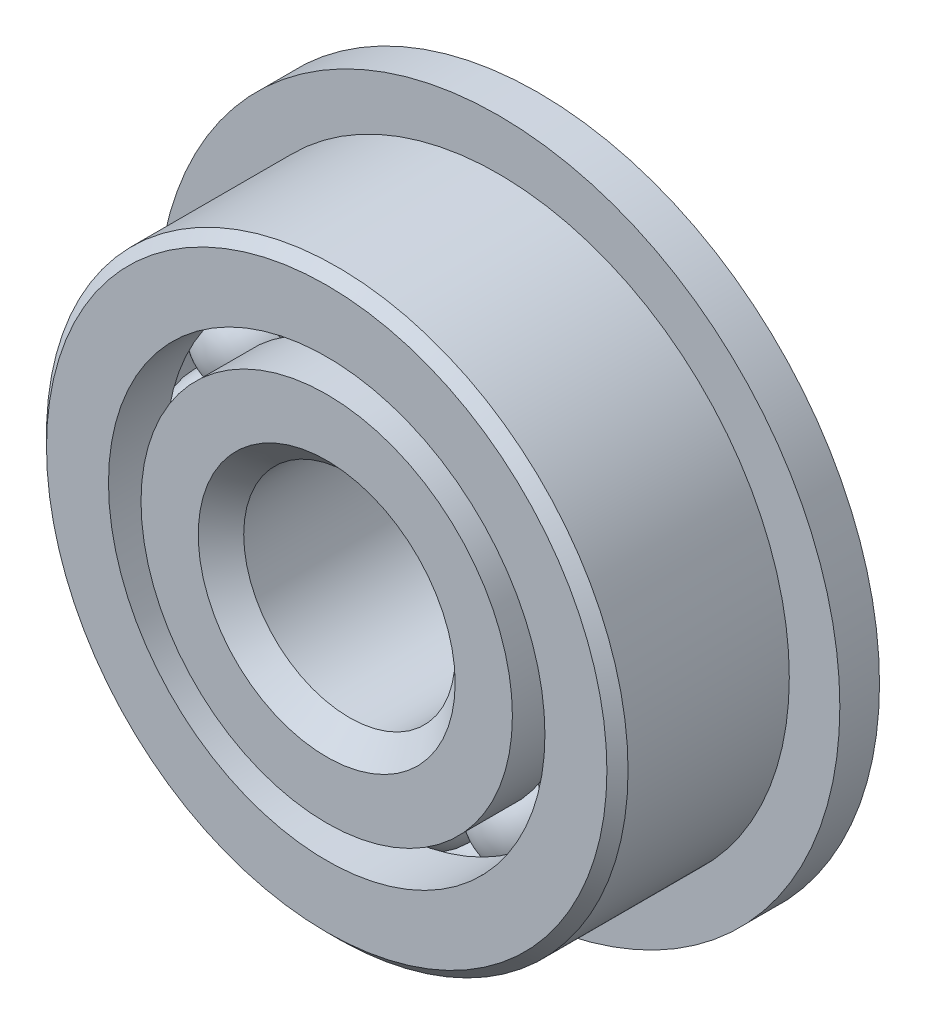
SolidWorks part; units mm, degrees
ref_plane "Front Plane" through (0, 0, 0) normal (0, 0, 1) x (1, 0, 0)
ref_plane "Top Plane" through (0, 0, 0) normal (0, 1, 0) x (1, 0, 0)
ref_plane "Right Plane" through (0, 0, 0) normal (1, 0, 0) x (0, 0, -1)
sketch "Sketch1" plane through (0, 0, 0) normal (1, 0, 0) x (0, 0, -1)
  line L0 (-3.175, 0) -> (3.175, 0) construction
  line L1 (0, 8.7312) -> (0, -8.7312) construction
  line L2 (2.8575, 8.7312) -> (-2.8575, 8.7312)
  line L3 (-2.8575, 8.7312) -> (-3.175, 8.4138)
  line L4 (-3.175, 8.4138) -> (-3.175, 6.5527)
  line L5 (-3.175, 6.5527) -> (-1.4436, 6.5527)
  line L6 (3.175, 6.5527) -> (1.4436, 6.5527)
  line L7 (3.175, 8.4138) -> (3.175, 6.5527)
  line L8 (2.8575, 8.7312) -> (3.175, 8.4138)
  line L9 (0, 8.7312) -> (0, 6.0643) construction
  line L11 (3.175, 0) -> (4.7625, 0) construction
  arc A0 (-1.4436, 6.5527) -> (1.4436, 6.5527) centre (0, 6.0643) cw
  circle A1 centre (0, 6.0643) radius 1.524 construction
  point P14 (0, 3.175)
  dimension "D3" = 3.048
  dimension "D1" = 45
  dimension "Width" = 6.35
  dimension "OD" = 17.4625
  dimension "D2" = 0.3175
  dimension "Shaft Dia" = 6.35
  dimension "D4" = 0.4885
  dimension "D5" = 2.667
  dimension "Total Wd" = 7.9375
revolve "Revolve1" add sketch "Sketch1" angle 360 about L0
sketch "Sketch2" plane through (0, 0, 0) normal (1, 0, 0) x (0, 0, -1)
  line L0 (-3.175, 5.5758) -> (-1.4436, 5.5758)
  line L1 (-3.175, 8.4138) -> (-3.175, -8.4138) construction
  line L2 (-3.175, 5.5758) -> (-3.175, 4.7167)
  line L3 (-3.175, 4.7167) -> (-2.3159, 3.8576)
  line L4 (-2.3159, 3.8576) -> (0, 3.8576)
  line L5 (0, 8.7312) -> (0, -8.7312) construction
  line L6 (0, 3.8576) -> (0, 4.5403)
  line L7 (0, 4.5403) -> (0, 3.175) construction
  line L8 (-3.175, 5.5758) -> (-3.175, 3.8576) construction
  line L9 (-3.175, 3.8576) -> (-2.3159, 3.8576) construction
  arc A0 (-1.4436, 5.5758) -> (0, 4.5403) centre (0, 6.0643) ccw
  arc A1 (1.4436, 6.5527) -> (-1.4436, 6.5527) centre (0, 6.0643) ccw construction
  circle A2 centre (0, 6.0643) radius 1.524 construction
  dimension "D1" = 45
revolve "Revolve2" add sketch "Sketch2" angle 360 about L0
sketch "Sketch3" plane through (0, 0, 0) normal (1, 0, 0) x (0, 0, -1)
  line L0 (-3.175, 4.7167) -> (-2.3159, 3.8576)
  line L1 (-2.3159, 3.8576) -> (0, 3.8576)
  line L2 (0, 3.8576) -> (0, 4.5403)
  line L3 (-3.175, 4.7167) -> (-3.175, 3.8576)
  line L4 (-3.175, 5.5758) -> (-3.175, 3.8576) construction
  line L5 (-3.175, 3.8576) -> (-2.4924, 3.175)
  line L6 (-2.4924, 3.175) -> (4.445, 3.175)
  line L8 (4.445, 3.175) -> (4.7625, 3.4925)
  line L10 (4.7625, 3.4925) -> (4.7625, 5.5758)
  line L11 (4.7625, 5.5758) -> (1.4436, 5.5758)
  line L13 (2.8575, 8.7312) -> (3.175, 8.4138) construction
  circle A0 centre (0, 6.0643) radius 1.524 construction
  arc A1 (1.4436, 5.5758) -> (0, 4.5403) centre (0, 6.0643) cw
revolve "Revolve3" add sketch "Sketch3" angle 360 about L0
sketch "Sketch4" plane through (0, 0, 0) normal (1, 0, 0) x (0, 0, -1)
  line L0 (-1.524, 6.0643) -> (1.524, 6.0643)
  circle A1 centre (0, 6.0643) radius 1.524 construction
  arc A2 (-1.524, 6.0643) -> (1.524, 6.0643) centre (0, 6.0643) cw
  arc A3 (1.4436, 6.5527) -> (-1.4436, 6.5527) centre (0, 6.0643) ccw construction
revolve "Revolve4" add sketch "Sketch4" angle 360 about L0
ref_axis "Axis1" through (0, 0, -3.175) along (0, 0, 1)
pattern_circular "CirPattern1" count 12 every 30 about axis through (0, 0, -3.175) along (0, 0, 1) of bodies 104
sketch "Sketch5" plane through (0, 0, 0) normal (1, 0, 0) x (0, 0, -1)
  line L0 (3.175, 8.4138) -> (3.175, 6.5527) construction
  line L1 (3.175, 7.4832) -> (1.9844, 7.4832)
  line L2 (3.175, 7.4832) -> (3.175, 10.2489)
  line L3 (3.175, 10.2489) -> (1.9844, 10.2489)
  line L4 (1.9844, 7.4832) -> (1.9844, 10.2489)
  line L5 (4.7625, 0) -> (-3.175, 0) construction
  dimension "Flange Thickness" = 1.1906
  dimension "Flange OD" = 20.4978
revolve "Revolve5" add sketch "Sketch5" angle 360 about L5
equation "\"D2@Sketch1\" = \"Width@Sketch1\"*.05"
equation "\"D4@Sketch1\" = (((\"OD@Sketch1\"-\"Width@Sketch1\")/2)/3.25)/3.5"
equation "\"D2@CirPattern1\" = 360/\"Balls@CirPattern1\""
equation "\"D5@Sketch1\" = \"D3@Sketch1\" * 7/8"
